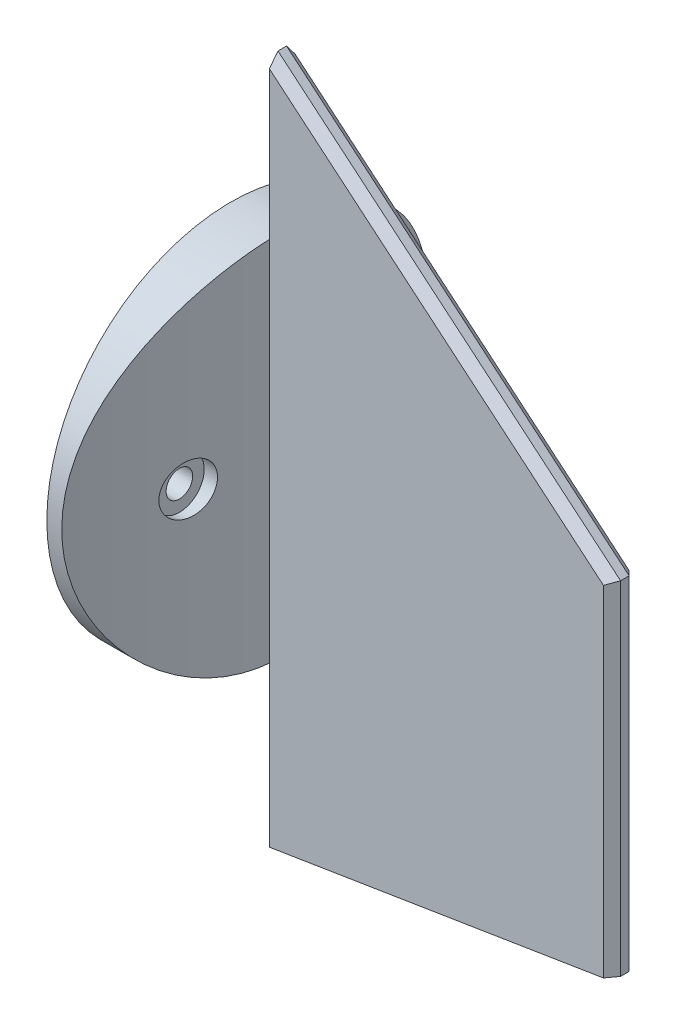
SolidWorks part; units mm, degrees
ref_plane "Front Plane" through (0, 0, 0) normal (0, 0, 1) x (1, 0, 0)
ref_plane "Top Plane" through (0, 0, 0) normal (0, 1, 0) x (1, 0, 0)
ref_plane "Right Plane" through (0, 0, 0) normal (1, 0, 0) x (0, 0, -1)
sketch "Sketch13" plane through (0, 0, 0) normal (1, 0, 0) x (0, 0, -1)
  line L0 (-2.6217, -2.2425) -> (-1.8172, -14.1833)
  line L1 (2.1766, -14.1326) -> (2.6778, -2.1753)
  arc A0 (2.6778, -2.1753) -> (-2.6217, -2.2425) centre (0, 0) ccw
  arc A1 (-1.8172, -14.1833) -> (2.1766, -14.1326) centre (0.1783, -14.0489) ccw
  circle A2 centre (0, 0) radius 16.3675
  dimension "D1" = 3.45
  dimension "D2" = 2
  dimension "D6" = 32.735
  dimension "D3" = 0.1783
  dimension "D4" = 2.1766
  dimension "D5" = 2.6778
extrude "Boss-Extrude11" add sketch "Sketch13" along normal mid plane 1.524
sketch "Sketch14" plane through (0.762, 0, 0) normal (1, 0, 0) x (0, 0, -1)
  circle A0 centre (0, 0) radius 16.3675
  circle A1 centre (0, 0) radius 16.3675 construction
extrude "Boss-Extrude12" add sketch "Sketch14" along normal mid plane 1.016
sketch "Sketch15" plane through (0, 0, 0) normal (0, 0, 1) x (1, 0, 0)
  line L0 (1.27, 18.3324) -> (1.27, -21.3321) construction
  line L1 (1.27, 0) -> (1.27, 25.4)
  line L2 (1.27, -16.3675) -> (1.27, 16.3675) construction
  line L3 (1.27, 0) -> (1.27, -25.4)
  line L4 (1.27, -25.4) -> (26.67, -21.3131)
  line L5 (26.67, -21.3131) -> (26.67, 4.0869)
  line L6 (26.67, 4.0869) -> (1.27, 25.4)
  dimension "D1" = 50
  dimension "D2" = 25.4
  dimension "D3" = 25.4
  dimension "D4" = 25.4
  dimension "D5" = 25.4
extrude "Boss-Extrude13" add sketch "Sketch15" along normal mid plane 1.905
fillet "Chamfer6" radius 0.762 4 edges at (13.97, 14.7434, -0.9525) (26.67, -8.6131, -0.9525) (26.67, -8.6131, 0.9525) (13.97, 14.7434, 0.9525) profile chamfer
sketch "Sketch20" plane through (-0.762, 0, 0) normal (-1, 0, 0) x (0, 0, 1)
  line L2 (1.8172, -14.1833) -> (2.6217, -2.2425)
  line L3 (-2.6778, -2.1753) -> (-2.1766, -14.1326)
  line L4 (1.8172, -14.1833) -> (2.6217, -2.2425)
  line L5 (-2.6778, -2.1753) -> (-2.1766, -14.1326)
  circle A1 centre (0, 0) radius 16.3675
  circle A2 centre (0, 0) radius 16.3675
  arc A4 (2.6217, -2.2425) -> (-2.6778, -2.1753) centre (0, 0) ccw
  arc A5 (-2.1766, -14.1326) -> (1.8172, -14.1833) centre (-0.1783, -14.0489) ccw
  arc A6 (2.6217, -2.2425) -> (-2.6778, -2.1753) centre (0, 0) ccw
  arc A7 (-2.1766, -14.1326) -> (1.8172, -14.1833) centre (-0.1783, -14.0489) ccw
  dimension "D1" = 0
  dimension "D2" = 0
sketch "Sketch26" plane through (0.254, 0, 0) normal (-1, 0, 0) x (0, 0, 1)
  line L2 (-2.6778, -2.1753) -> (-2.1766, -14.1326)
  line L3 (1.8172, -14.1833) -> (2.6217, -2.2425)
  line L4 (-2.6778, -2.1753) -> (-2.1766, -14.1326)
  line L5 (1.8172, -14.1833) -> (2.6217, -2.2425)
  arc A2 (2.6217, -2.2425) -> (-2.6778, -2.1753) centre (0, 0) ccw
  arc A3 (-2.1766, -14.1326) -> (1.8172, -14.1833) centre (-0.1783, -14.0489) ccw
  arc A4 (2.6217, -2.2425) -> (-2.6778, -2.1753) centre (0, 0) ccw
  arc A5 (-2.1766, -14.1326) -> (1.8172, -14.1833) centre (-0.1783, -14.0489) ccw
  dimension "D1" = 0
extrude "Boss-Extrude19" add sketch "Sketch26" along normal up to surface (1.016 mm away) up to face at (-0.762, 0, -16.3675)
sketch "Sketch27" plane through (1.27, 0, 0) normal (1, 0, 0) x (0, 0, -1)
  line L1 (0.9525, 16.3398) -> (0.9525, -16.3398)
  line L3 (0.9525, 16.3398) -> (0.9525, -16.3398)
  line L5 (-0.9525, -16.3398) -> (-0.9525, 16.3398)
  line L6 (-0.9525, -16.3398) -> (-0.9525, 16.3398)
  arc A1 (0.9525, -16.3398) -> (0.9525, 16.3398) centre (0, 0) ccw
  arc A2 (0.9525, -16.3398) -> (0.9525, 16.3398) centre (0, 0) ccw
  arc A3 (-0.9525, 16.3398) -> (-0.9525, -16.3398) centre (0, 0) ccw
  arc A4 (-0.9525, 16.3398) -> (-0.9525, -16.3398) centre (0, 0) ccw
  dimension "D1" = 0
  dimension "D2" = 0
extrude "Boss-Extrude20" add sketch "Sketch27" along normal blind 1.524
sketch "Sketch28" plane through (2.794, 0, 0) normal (1, 0, 0) x (0, 0, -1)
  line L0 (-23.2899, 0) -> (37.7845, 0) construction
  line L1 (-16.3675, 18.2766) -> (-16.3675, 10.7478) construction
  line L2 (0, 0) -> (0, -28.4596) construction
  circle A0 centre (-7.6248, 0) radius 2.2098
  arc A1 (-0.9525, 16.3398) -> (-0.9525, -16.3398) centre (0, 0) ccw construction
  circle A2 centre (7.6248, 0) radius 2.2098
  dimension "D1" = 4.4196
  dimension "D2" = 8.7427
extrude "Cut-Extrude9" cut sketch "Sketch28" against normal blind 1.524
sketch "Sketch29" plane through (1.27, 0, 0) normal (1, 0, 0) x (0, 0, -1)
  circle A0 centre (-7.6248, 0) radius 1.1811
  circle A1 centre (7.6248, 0) radius 1.1811
  dimension "D1" = 2.3622
  dimension "D2" = 2.3622
extrude "Cut-Extrude10" cut sketch "Sketch29" against normal blind 14.224
sketch "Sketch31" plane through (2.794, 0, 0) normal (1, 0, 0) x (0, 0, -1)
  line L0 (0.9525, 16.3398) -> (0.9525, -16.3398) construction
  line L1 (-0.9525, -16.3398) -> (-0.9525, 16.3398) construction
  line L2 (0.9525, 16.3398) -> (0.9525, -16.3398)
  line L3 (-0.9525, -16.3398) -> (-0.9525, 16.3398)
  circle A0 centre (7.6248, 0) radius 2.2098 construction
  circle A1 centre (-7.6248, 0) radius 2.2098
  circle A2 centre (-7.6248, 0) radius 2.2098
  circle A3 centre (7.6248, 0) radius 2.2098
  arc A4 (0.9525, -16.3398) -> (0.9525, 16.3398) centre (0, 0) ccw construction
  arc A5 (-0.9525, 16.3398) -> (-0.9525, -16.3398) centre (0, 0) ccw construction
  arc A6 (0.9525, -16.3398) -> (0.9525, 16.3398) centre (0, 0) ccw
  arc A7 (-0.9525, 16.3398) -> (-0.9525, -16.3398) centre (0, 0) ccw
  dimension "D1" = 0
sketch "Sketch32" plane through (-0.762, 0, 0) normal (-1, 0, 0) x (0, 0, 1)
  circle A0 centre (-7.6248, 0) radius 1.1811 construction
  circle A1 centre (-7.6248, 0) radius 1.1811
  circle A2 centre (7.6248, 0) radius 1.1811 construction
  circle A3 centre (7.6248, 0) radius 1.1811
  circle A5 centre (0, 0) radius 16.3675
  circle A6 centre (0, 0) radius 16.3675
  dimension "D1" = 0
sketch "Sketch35" plane through (2.794, 0, 0) normal (1, 0, 0) x (0, 0, -1)
  circle A0 centre (0, 0) radius 16.3675
  circle A1 centre (0, 0) radius 32.2294
extrude "Cut-Extrude15" cut sketch "Sketch35" along normal blind 52.832 contours A0
sketch "Sketch36" plane through (2.794, 0, 0) normal (1, 0, 0) x (0, 0, -1)
  circle A0 centre (0, 0) radius 29.1724
  circle A1 centre (0, 0) radius 16.3675
extrude "Cut-Extrude16" cut sketch "Sketch36" against normal blind 52.832 and the other way blind 52.832
sketch "Sketch33" plane through (0, 0, 0) normal (0, 1, 0) x (1, 0, 0)
  line L0 (-3.8217, 0) -> (38.6284, 0) construction
  line L2 (2.794, -16.3675) -> (2.794, 16.3675) construction
  line L3 (2.794, 16.3675) -> (-0.762, 16.3675) construction
  line L4 (-0.4519, 16.3675) -> (-0.762, 16.3675)
  line L5 (-0.4519, 16.3675) -> (-0.4519, -16.3675)
  line L6 (-0.4519, -16.3675) -> (-0.762, -16.3675)
  line L7 (-0.762, 16.3675) -> (-0.762, -16.3675)
  line L9 (-0.4519, 16.3675) -> (2.794, 16.3675)
  line L10 (-0.4519, 16.3675) -> (-0.4519, -16.3675)
  line L11 (-0.4519, -16.3675) -> (2.794, -16.3675)
  line L12 (2.794, 16.3675) -> (2.794, -16.3675)
  circle A0 centre (-40.0958, 0) radius 42.8898
  dimension "D1" = 85.7797
extrude "Cut-Extrude17" cut sketch "Sketch33" against normal blind 52.832 and the other way blind 52.832 contours A0 L11 L12 | A0 L12 L9 region at (1.8269, 0, -12.3072) region at (1.8269, 0, 12.3072)
ref_plane "Plane6" through (0, 0, 0) normal (0, 0, -1) x (-1, 0, 0)
sketch "Sketch38" plane through (0, 0, 0) normal (0, 0, -1) x (-1, 0, 0)
  line L0 (-2.794, 0) -> (-2.794, 30.48)
  line L1 (-2.794, 16.3675) -> (-2.794, -16.3675) construction
  line L2 (-2.794, 30.48) -> (-2.794, 0)
  line L3 (-2.794, 0) -> (-2.794, -30.48)
  line L4 (-2.794, -30.48) -> (-33.274, -25.5758)
  line L5 (-33.274, -25.5758) -> (-33.274, 4.9042)
  line L6 (-33.274, 4.9042) -> (-2.794, 30.48)
  line L7 (-2.794, 30.48) -> (-38.6624, 30.48) construction
  dimension "D1" = 30.48
  dimension "D2" = 30.48
  dimension "D3" = 40
  dimension "D4" = 30.48
  dimension "D5" = 30.48
extrude "Boss-Extrude21" add sketch "Sketch38" along normal mid plane 2.286 separate body contours L6 L5 L4 L3 L0 region at (16.3407, -4.5937, 0)
fillet "Chamfer7" radius 0.762 4 edges at (33.274, -10.3358, 1.143) (33.274, -10.3358, -1.143) (18.034, 17.6921, -1.143) (18.034, 17.6921, 1.143) profile chamfer
sketch "Sketch39" plane through (-0.762, 0, 0) normal (-1, 0, 0) x (0, 0, 1)
  circle A1 centre (0, 0) radius 16.3675
  circle A2 centre (0, 0) radius 16.3675
  dimension "D1" = 0
sketch "Sketch41" plane through (-0.762, 0, 0) normal (-1, 0, 0) x (0, 0, 1)
  circle A0 centre (0, 0) radius 2.921
  circle A1 centre (0, 0) radius 16.3675
  circle A2 centre (0, 0) radius 16.3675
  dimension "D2" = 5.842
  dimension "D1" = 0
extrude "Cut-Extrude19" cut sketch "Sketch41" against normal blind 1.524 contours A0 region at (-0.762, 0, 0)
sketch "Sketch42" plane through (-0.762, 0, 0) normal (-1, 0, 0) x (0, 0, 1)
  circle A0 centre (0, 0) radius 4.064
  dimension "D1" = 8.128
extrude "Cut-Extrude20" cut sketch "Sketch42" against normal mid plane 1.524
sketch "Sketch43" plane through (0.762, 0, 0) normal (-1, 0, 0) x (0, 0, 1)
  circle A1 centre (0, 0) radius 2.921
  circle A2 centre (0, 0) radius 2.921
  dimension "D1" = 0
extrude "Cut-Extrude21" cut sketch "Sketch43" against normal mid plane 1.016
sketch "Sketch44" plane through (0, 0, 0) normal (-1, 0, 0) x (0, 0, 1)
  circle A3 centre (0, 0) radius 5.4102
  point P1 (-13.1272, -0.9257)
  point P7 (-25.1158, -0.1986)
  dimension "D3" = 10.8204
extrude "Cut-Extrude24" cut sketch "Sketch44" against normal blind 0.9398 and the other way blind 0.9398
sketch "Sketch46" plane through (1.27, 0, 0) normal (-1, 0, 0) x (0, 0, 1)
  circle A1 centre (0, 0) radius 2.921
  circle A2 centre (0, 0) radius 2.921
  dimension "D1" = 0
extrude "Cut-Extrude25" cut sketch "Sketch46" against normal blind 0.508
sketch "Sketch47" plane through (-0.762, 0, 0) normal (-1, 0, 0) x (0, 0, 1)
  circle A0 centre (7.6248, 0) radius 1.1811 construction
  circle A1 centre (0, 0) radius 16.3675
  circle A2 centre (0, 0) radius 16.3675
  circle A3 centre (-7.6248, 0) radius 1.1811 construction
  circle A4 centre (0, 0) radius 5.4102 construction
  circle A5 centre (7.6248, 0) radius 1.1811
  circle A6 centre (-7.6248, 0) radius 1.1811
  circle A7 centre (0, 0) radius 5.4102
  dimension "D1" = 0
extrude "Boss-Extrude22" add sketch "Sketch47" along normal blind 1.016
sketch "Sketch48" plane through (0.9398, 0, 0) normal (-1, 0, 0) x (0, 0, 1)
  circle A0 centre (0, 0) radius 2.921 construction
  circle A1 centre (0, 0) radius 5.4102
  circle A2 centre (0, 0) radius 5.4102
  circle A3 centre (0, 0) radius 2.921
  dimension "D1" = 0
extrude "Boss-Extrude23" add sketch "Sketch48" along normal blind 1.524
sketch "Sketch49" plane through (1.778, 0, 0) normal (-1, 0, 0) x (0, 0, 1)
  circle A1 centre (0, 0) radius 2.921
  circle A2 centre (0, 0) radius 2.921
  dimension "D1" = 0
extrude "Boss-Extrude24" add sketch "Sketch49" along normal blind 0.762
sketch "Sketch51" plane through (-0.5842, 0, 0) normal (-1, 0, 0) x (0, 0, 1)
  circle A1 centre (0, 0) radius 5.4102
  circle A2 centre (0, 0) radius 5.4102
  dimension "D1" = 0
extrude "Cut-Extrude26" cut sketch "Sketch51" against normal up to surface (1.6002 mm away) up to face at (1.016, 0, 2.921)
sketch "Sketch53" plane through (0, 0, 0) normal (1, 0, 0) x (0, 0, -1)
  circle A0 centre (-7.6248, 0) radius 2.2098
sketch "Sketch17" plane through (0, 0, 0) normal (0, 1, 0) x (1, 0, 0)
  line L0 (2.7484, 0) -> (76.4286, 0) construction
  line L1 (1.27, -0.1905) -> (1.27, 0.1905) construction
  line L3 (-0.762, 16.3675) -> (1.27, 16.3675)
  line L4 (-0.762, 16.3675) -> (-0.762, -16.3675)
  line L5 (-0.4519, 0) -> (-0.762, 0) construction
  line L6 (-0.762, -16.3675) -> (1.27, -16.3675)
  line L7 (1.27, 16.3675) -> (1.27, -16.3675)
  circle A0 centre (-38.5818, 0) radius 39.8518
  point P3 (1.27, 0)
  dimension "D1" = 79.7036
extrude "Cut-Extrude5" [suppressed] cut sketch "Sketch17" against normal mid plane 50.8 contours A0 L4 L6 L7 | A0 L7 L3 L4
sketch "Sketch18" plane through (-0.762, 0, 0) normal (-1, 0, 0) x (0, 0, 1)
  line L0 (-2.803, -2.2222) -> (-2.3035, -14.138)
  line L1 (1.9439, -14.1919) -> (2.7457, -2.2927)
  line L2 (-2.6778, -2.1753) -> (-2.1766, -14.1326)
  line L3 (1.8172, -14.1833) -> (2.6217, -2.2425)
  line L4 (-2.6778, -2.1753) -> (-2.1766, -14.1326)
  line L5 (1.8172, -14.1833) -> (2.6217, -2.2425)
  arc A0 (2.7457, -2.2927) -> (-2.803, -2.2222) centre (0, 0) ccw
  arc A1 (-2.3035, -14.138) -> (1.9439, -14.1919) centre (-0.1783, -14.0489) ccw
  arc A2 (2.6217, -2.2425) -> (-2.6778, -2.1753) centre (0, 0) ccw
  arc A3 (-2.1766, -14.1326) -> (1.8172, -14.1833) centre (-0.1783, -14.0489) ccw
  arc A4 (2.6217, -2.2425) -> (-2.6778, -2.1753) centre (0, 0) ccw
  arc A5 (-2.1766, -14.1326) -> (1.8172, -14.1833) centre (-0.1783, -14.0489) ccw
  dimension "D1" = 0
  dimension "D2" = 0.127
extrude "Cut-Extrude6" [suppressed] cut sketch "Sketch18" against normal up to surface (1.016 mm away) up to face at (33.274, -10.3358, 0)
sketch "Sketch19" [suppressed] plane through (-0.762, 0, 0) normal (-1, 0, 0) x (0, 0, 1)
  line L2 (-12.563, 10.4913) -> (-12.563, -10.4913)
  line L3 (12.563, -10.4913) -> (12.563, 10.4913)
  line L4 (-12.563, 10.4913) -> (-12.563, -10.4913)
  line L5 (12.563, -10.4913) -> (12.563, 10.4913)
  line L6 (-2.803, -2.2222) -> (-2.3035, -14.138)
  line L7 (1.9439, -14.1919) -> (2.7457, -2.2927)
  line L8 (-2.803, -2.2222) -> (-2.3035, -14.138)
  line L9 (1.9439, -14.1919) -> (2.7457, -2.2927)
  arc A2 (-12.563, -10.4913) -> (12.563, -10.4913) centre (0, 0) ccw
  arc A3 (12.563, 10.4913) -> (-12.563, 10.4913) centre (0, 0) ccw
  arc A4 (-12.563, -10.4913) -> (12.563, -10.4913) centre (0, 0) ccw
  arc A5 (12.563, 10.4913) -> (-12.563, 10.4913) centre (0, 0) ccw
  arc A6 (2.7457, -2.2927) -> (-2.803, -2.2222) centre (0, 0) ccw
  arc A7 (-2.3035, -14.138) -> (1.9439, -14.1919) centre (-0.1783, -14.0489) ccw
  arc A8 (2.7457, -2.2927) -> (-2.803, -2.2222) centre (0, 0) ccw
  arc A9 (-2.3035, -14.138) -> (1.9439, -14.1919) centre (-0.1783, -14.0489) ccw
  dimension "D1" = 0
  dimension "D2" = 0
extrude "Boss-Extrude15" [suppressed] add sketch "Sketch19" along normal blind 2.54
